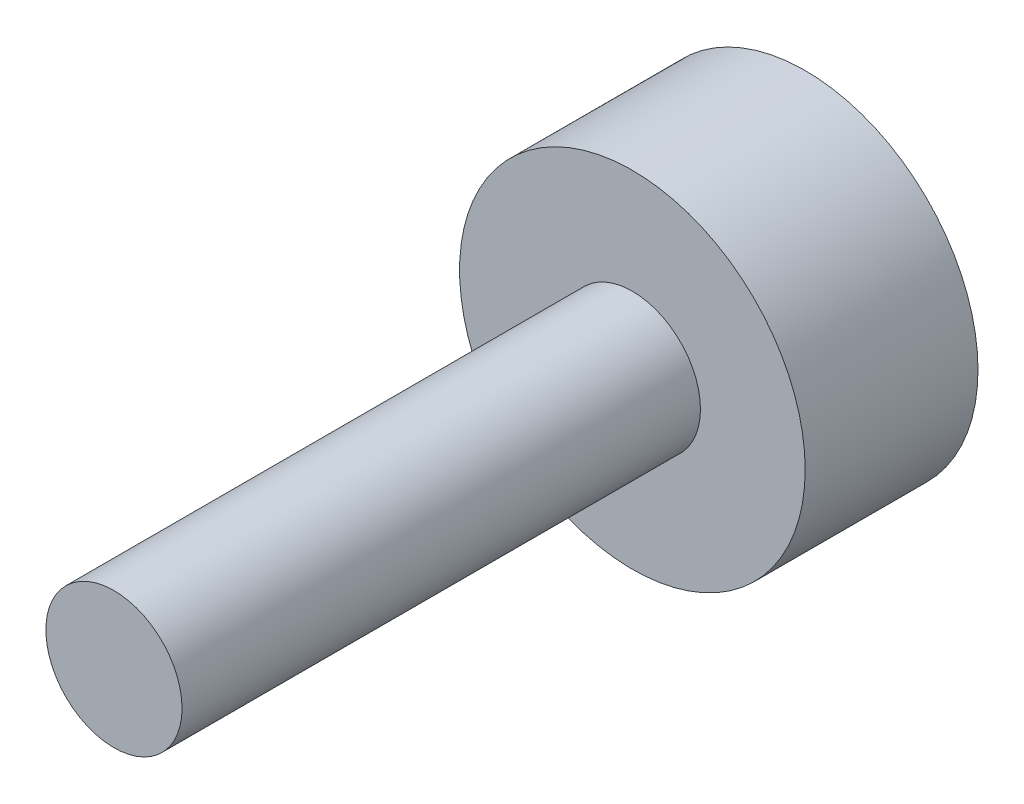
SolidWorks part; units mm, degrees
material "ABS P400"
ref_plane "Front Plane" through (0, 0, 0) normal (0, 0, 1) x (1, 0, 0)
ref_plane "Top Plane" through (0, 0, 0) normal (0, 1, 0) x (1, 0, 0)
ref_plane "Right Plane" through (0, 0, 0) normal (1, 0, 0) x (0, 0, -1)
sketch "Sketch1" plane through (0, 0, 0) normal (0, 0, 1) x (1, 0, 0)
  circle A0 centre (0, 0) radius 5
  dimension "D1" = 10
extrude "Boss-Extrude1" add sketch "Sketch1" along normal mid plane 5
sketch "Sketch2" plane through (0, 0, 2.5) normal (0, 0, 1) x (1, 0, 0)
  circle A0 centre (0, 0) radius 1.97
  dimension "D1" = 3.94
extrude "Boss-Extrude2" add sketch "Sketch2" along normal blind 15
